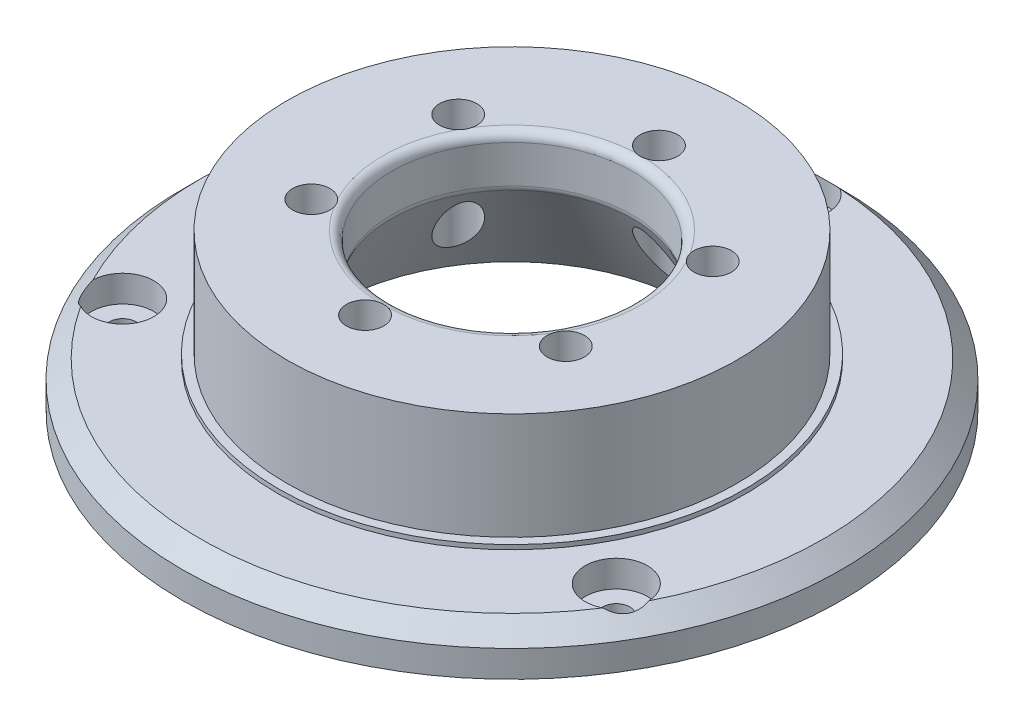
SolidWorks part; units mm, degrees
ref_plane "Front Plane" through (0, 0, 0) normal (0, 0, 1) x (1, 0, 0)
ref_plane "Top Plane" through (0, 0, 0) normal (0, 1, 0) x (1, 0, 0)
ref_plane "Right Plane" through (0, 0, 0) normal (1, 0, 0) x (0, 0, -1)
sketch "Sketch1" plane through (0, 0, 0) normal (0, 1, 0) x (1, 0, 0)
  circle A0 centre (0, 0) radius 25.25
  circle A1 centre (0, 0) radius 13.5
  dimension "D1" = 50.5
  dimension "D2" = 27
extrude "Boss-Extrude1" add sketch "Sketch1" along normal blind 12.5
sketch "Sketch2" plane through (0, 0, 0) normal (0, 1, 0) x (1, 0, 0)
  circle A0 centre (0, 0) radius 37
  circle A1 centre (0, 0) radius 13.5
  circle A2 centre (0, 0) radius 13.5 construction
  dimension "D1" = 74
extrude "Boss-Extrude2" add sketch "Sketch2" against normal blind 5
sketch "Sketch3" plane through (0, 0, 0) normal (0, 1, 0) x (1, 0, 0)
  circle A0 centre (0, 32) radius 1.5
  dimension "D2" = 3
  dimension "D1" = 32
extrude "Cut-Extrude1" cut sketch "Sketch3" against normal through all
sketch "Sketch4" plane through (0, 0, 0) normal (0, 1, 0) x (1, 0, 0)
  circle A0 centre (0, 32) radius 3.5
  dimension "D1" = 7
extrude "Cut-Extrude2" cut sketch "Sketch4" against normal blind 3 and the other way through all
pattern_circular "CirPattern1" count 3 over 360 about axis through (0, -5, 0) along (0, 1, 0) of "Cut-Extrude1", "Cut-Extrude2"
chamfer "Chamfer1" distance 12 angle 30 1 edges at (0, -5, 13.5) first distance on face at (0, 12.5, 13.5)
chamfer "Chamfer2" distance 2 angle 45 1 edges at (0, 0, 37)
sketch "Sketch5" plane through (0, 12.5, 0) normal (0, 1, 0) x (1, 0, 0)
  line L0 (0, 16.5) -> (0, 0) construction
  line L1 (0, 0) -> (0, 32) construction
  circle A0 centre (0, 16.5) radius 2.1
  dimension "D2" = 4.2
  dimension "D3" = 16.5
extrude "Cut-Extrude3" cut sketch "Sketch5" against normal through all
pattern_circular "CirPattern2" count 6 over 360 about axis through (0, 12.5, 0) along (0, -1, 0) of "Cut-Extrude3" reverse direction yes
fillet "Fillet1" radius 1 2 edges at (0, 12.5, 13.5) (0, 7, 13.5)
sketch "Sketch6" plane through (0, 0, 0) normal (0, 1, 0) x (1, 0, 0)
  circle A0 centre (0, 0) radius 26.25
  circle A1 centre (0, 0) radius 25.25
  circle A2 centre (0, 0) radius 25.25 construction
  dimension "D1" = 1
extrude "Boss-Extrude3" add sketch "Sketch6" along normal blind 0.5
